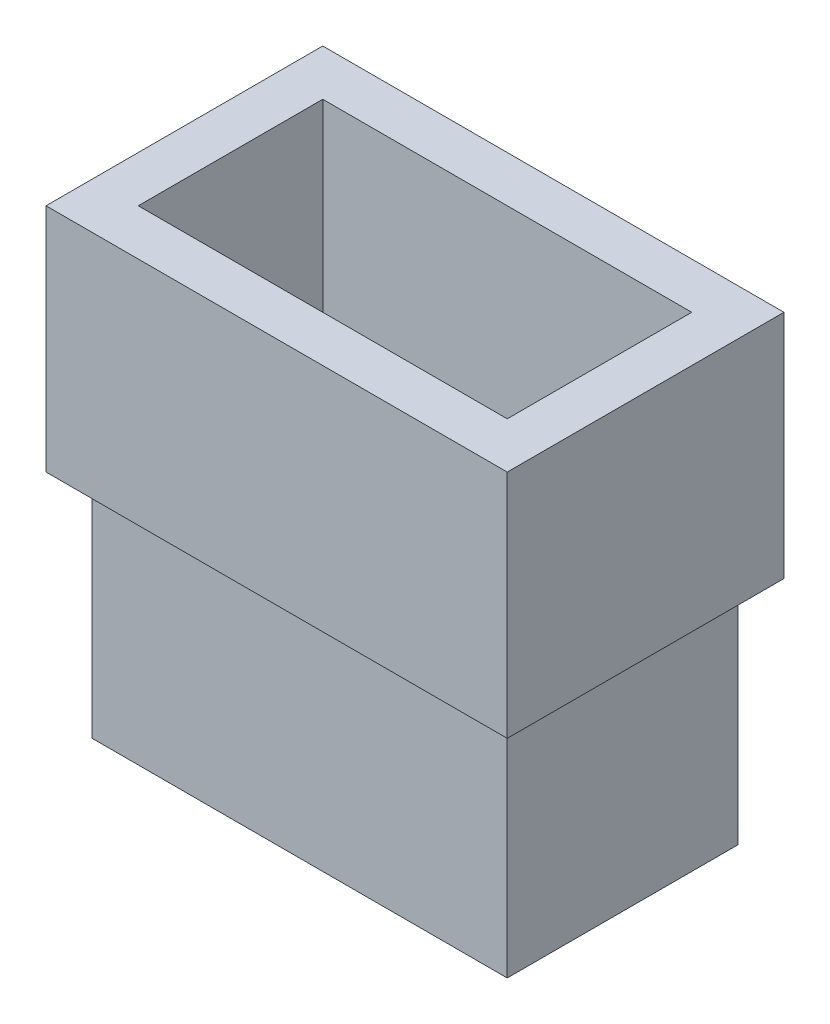
SolidWorks part; units mm, degrees
material "Delrin 2700 NC010, Low Viscosity Acetal Copolymer (SS)"
ref_plane "Front" through (0, 0, 0) normal (0, 0, 1) x (1, 0, 0)
ref_plane "Top" through (0, 0, 0) normal (0, 1, 0) x (1, 0, 0)
ref_plane "Right" through (0, 0, 0) normal (1, 0, 0) x (0, 0, -1)
sketch "Sketch1" plane through (0, 0, 0) normal (0, 1, 0) x (1, 0, 0)
  line L0 (22.5, -12.5) -> (22.5, 12.5)
  line L1 (-25, -15) -> (25, -15)
  line L2 (-25, -15) -> (-25, 15)
  line L3 (-25, 15) -> (25, 15)
  line L4 (25, -15) -> (25, 15)
  line L5 (-25, -15) -> (25, 15) construction
  line L6 (-25, 15) -> (25, -15) construction
  line L7 (-20, -10) -> (20, -10)
  line L8 (-20, -10) -> (-20, 10)
  line L9 (-20, 10) -> (20, 10)
  line L10 (20, -10) -> (20, 10)
  line L11 (-20, -10) -> (20, 10) construction
  line L12 (-20, 10) -> (20, -10) construction
  line L13 (-22.5, 12.5) -> (22.5, 12.5)
  line L14 (-22.5, -12.5) -> (-22.5, 12.5)
  line L15 (-22.5, -12.5) -> (22.5, -12.5)
  point P0 (0, 0)
  point P6 (0, 0)
  point P15 (20, 8.4936)
  dimension "D1" = 50
  dimension "D2" = 5
  dimension "D3" = 2.5
  dimension "D4" = 30
  dimension "D5" = 2.5
extrude "Boss-Extrude1" add sketch "Sketch1" along normal blind 25 contours L14 L15 L0 L13 L10 L7 L8 L9 | L1 L4 L3 L2 L15 L14 L13 L0 region at (0, 0, 11.9852) region at (-24.4169, 0, 0)
extrude "Boss-Extrude2" add sketch "Sketch1<3>" against normal blind 25 contours L14 L15 L0 L13 L10 L7 L8 L9 region at (0, 0, 11.9852)
sketch "Sketch1<3>" plane through (0, 0, 0) normal (0, 1, 0) x (1, 0, 0) same geometry as "Sketch1"
